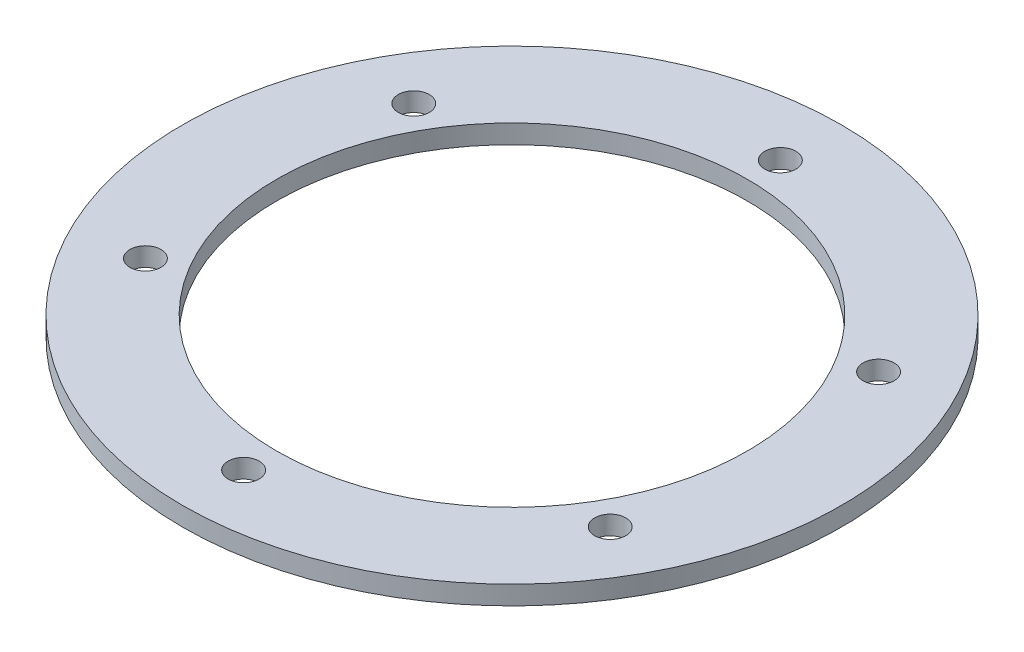
SolidWorks part; units mm, degrees
note: '?' marks a value the reader was unsure of.
material "黄铜"
ref_plane "前视基准面" through (0, 0, 0) normal (0, 0, 1) x (1, 0, 0)
ref_plane "上视基准面" through (0, 0, 0) normal (0, 1, 0) x (1, 0, 0)
ref_plane "右视基准面" through (0, 0, 0) normal (1, 0, 0) x (0, 0, -1)
sketch "草图1" plane through (0, 0, 0) normal (0, 1, 0) x (1, 0, 0)
  circle A0 centre (0, 0) radius 35
  dimension "D1" = 70
extrude "凸台-拉伸1" add sketch "草图1" along normal blind 2
sketch "草图2" plane through (0, 2, 0) normal (0, 1, 0) x (1, 0, 0)
  circle A0 centre (0, 0) radius 25
  dimension "D1" = 50
extrude "切除-拉伸1" cut sketch "草图2" against normal blind 2
sketch "草图3" plane through (0, 2, 0) normal (0, 1, 0) x (1, 0, 0)
  circle A0 centre (0, 0) radius 28.5
  dimension "D1" = 57
ref_axis "基准轴1" through (0, 0, 0) along (0, 1, 0)?
hole_wizard "孔1" positions "草图4" profile "草图5" legacy end condition up to next
sketch "草图4" plane through (0, 2, 0) normal (0, 1, 0) x (1, 0, 0)
  circle A0 centre (0, 0) radius 28.5 construction
  point P0 (0, 28.5)
sketch "草图5" plane through (0, 2, -28.5) normal (1, 0, 0) x (0, 0, 1)
  line L0 (0, 0) -> (0, 2)
  line L1 (0, 2) -> (1.65, 2)
  line L2 (1.65, 2) -> (1.65, 0)
  line L3 (1.65, 0) -> (0, 0)
  line L4 (0, 110) -> (0, -10) construction
  dimension "直径" = 3.3
  dimension "深度" = 2
pattern_circular "阵列(圆周)1" count 6 every 60 about axis through (0, 0, 0) along (0, 1, 0) of "孔1"
